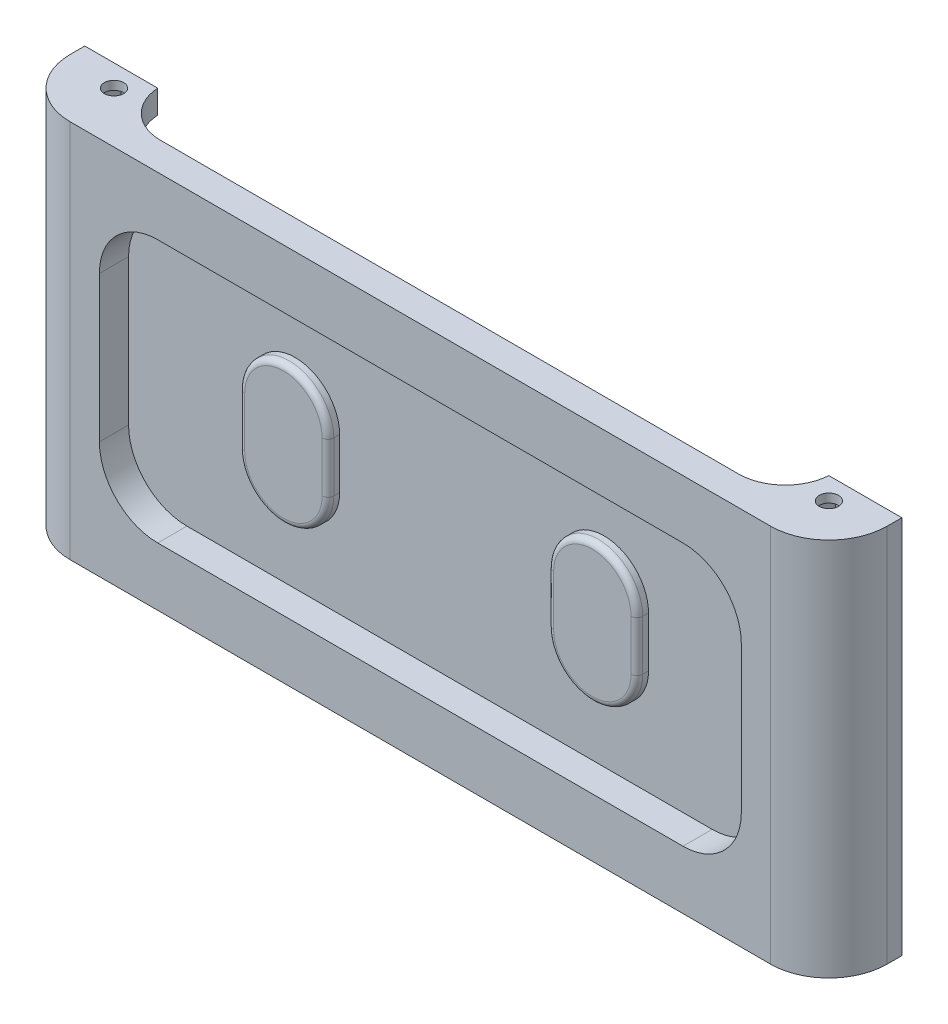
SolidWorks part; units mm, degrees
ref_plane "Front Plane" through (0, 0, 0) normal (0, 0, 1) x (1, 0, 0)
ref_plane "Top Plane" through (0, 0, 0) normal (0, 1, 0) x (1, 0, 0)
ref_plane "Right Plane" through (0, 0, 0) normal (1, 0, 0) x (0, 0, -1)
sketch "Sketch1" plane through (0, 0, 0) normal (0, 0, 1) x (1, 0, 0)
  line L1 (0, 0) -> (140, 0)
  line L2 (0, 0) -> (0, 65)
  line L3 (0, 65) -> (140, 65)
  line L4 (140, 0) -> (140, 65)
  dimension "D1" = 140
  dimension "D2" = 65
extrude "Boss-Extrude1" add sketch "Sketch1" along normal blind 12.5
sketch "Sketch4" plane through (0, 65, 0) normal (0, 1, 0) x (1, 0, 0)
  line L6 (5, 0) -> (135, 0)
  line L9 (135, 0) -> (135, -7.5)
  line L10 (5, -7.5) -> (5, 0)
  line L11 (135, -7.5) -> (5, -7.5)
  line L12 (135, 0) -> (135, -7.5)
  line L13 (5, -7.5) -> (5, 0)
  line L14 (135, -7.5) -> (5, -7.5)
  dimension "D1" = 5
extrude "Cut-Extrude3" cut sketch "Sketch4" against normal through all
sketch "Sketch2" plane through (0, 0, 12.5) normal (0, 0, 1) x (1, 0, 0)
  line L0 (70, 65) -> (70, 0) construction
  line L1 (140, 65) -> (0, 65) construction
  line L2 (0, 0) -> (140, 0) construction
  line L3 (140, 0) -> (140, 65) construction
  line L4 (15, 55) -> (125, 55)
  line L5 (15, 55) -> (15, 10)
  line L6 (15, 10) -> (125, 10)
  line L7 (125, 55) -> (125, 10)
  line L8 (15, 55) -> (125, 10) construction
  line L9 (15, 10) -> (125, 55) construction
  point P6 (70, 32.5)
  dimension "D1" = 15
  dimension "D2" = 10
extrude "Cut-Extrude1" cut sketch "Sketch2" against normal through all
fillet "Fillet1" radius 10 4 edges at (15, 10, 10) (15, 55, 10) (125, 10, 10) (125, 55, 10)
fillet "Fillet2" radius 10 2 edges at (140, 32.5, 12.5) (0, 32.5, 12.5)
sketch "Sketch5" plane through (0, 0, 0) normal (0, -1, 0) x (1, 0, 0)
  line L0 (0, 0) -> (5, 0) construction
  line L1 (5, 7.5) -> (12.5, 7.5)
  line L2 (5, 7.5) -> (5, 0)
  line L3 (5, 0) -> (12.5, 0)
  line L4 (12.5, 7.5) -> (12.5, 0)
  line L5 (135, 7.5) -> (127.5, 7.5)
  line L6 (135, 7.5) -> (135, 0)
  line L7 (135, 0) -> (127.5, 0)
  line L8 (127.5, 7.5) -> (127.5, 0)
extrude "Boss-Extrude2" add sketch "Sketch5" against normal blind 4
sketch "Sketch6" plane through (0, 4, 0) normal (0, 1, 0) x (1, 0, 0)
  line L0 (8.75, 0) -> (8.75, -7.5) construction
  line L1 (11.9254, -3.75) -> (10.3377, -1)
  line L2 (10.3377, -1) -> (7.1623, -1)
  line L3 (7.1623, -1) -> (5.5746, -3.75)
  line L4 (5.5746, -3.75) -> (7.1623, -6.5)
  line L5 (7.1623, -6.5) -> (10.3377, -6.5)
  line L6 (10.3377, -6.5) -> (11.9254, -3.75)
  line L7 (5, 0) -> (12.5, 0) construction
  line L8 (12.5, -7.5) -> (5, -7.5) construction
  line L9 (70, -12.5) -> (70, 1.5241) construction
  line L10 (130, -12.5) -> (10, -12.5) construction
  line L11 (134.4254, -3.75) -> (132.8377, -6.5)
  line L12 (132.8377, -6.5) -> (129.6623, -6.5)
  line L13 (129.6623, -6.5) -> (128.0746, -3.75)
  line L14 (128.0746, -3.75) -> (129.6623, -1)
  line L15 (129.6623, -1) -> (132.8377, -1)
  line L16 (132.8377, -1) -> (134.4254, -3.75)
  circle A0 centre (8.75, -3.75) radius 2.75 construction
  circle A1 centre (8.75, -3.75) radius 1.65
  circle A2 centre (131.25, -3.75) radius 1.65
  dimension "D1" = 3.3
  dimension "D2" = 5.5
extrude "Cut-Extrude5" cut sketch "Sketch6<2>" against normal through all contours A1 | A2 region at (8.75, 4, 3.75) region at (131.25, 4, 3.75)
sketch "Sketch6<2>" plane through (0, 4, 0) normal (0, 1, 0) x (1, 0, 0) same geometry as "Sketch6"
extrude "Cut-Extrude4" cut sketch "Sketch6" against normal blind 2.5
fillet "Fillet3" radius 8 2 edges at (127.5, 2, 7.5) (12.5, 2, 7.5)
ref_plane "Plane1" through (0, 32.5, 0) normal (0, 1, 0) x (1, 0, 0)
mirror "Mirror1" about plane through (0, 32.5, 0) normal (0, 1, 0) of "Cut-Extrude5", "Cut-Extrude4", "Boss-Extrude2", "Fillet3"
sketch "Sketch7" plane through (0, 0, 7.5) normal (0, 0, -1) x (-1, 0, 0)
  line L1 (-135, 61) -> (-5, 61)
  line L2 (-135, 61) -> (-135, 4)
  line L3 (-135, 4) -> (-5, 4)
  line L4 (-5, 61) -> (-5, 4)
extrude "Boss-Extrude3" add sketch "Sketch7" along normal blind 1 separate body
sketch "Sketch8" plane through (0, 0, 7.5) normal (0, 0, 1) x (1, 0, 0)
  line L0 (70, 55) -> (70, 24.7719) construction
  line L1 (115, 55) -> (25, 55) construction
  line L2 (25, 10) -> (115, 10) construction
  line L3 (43.5327, 36.6686) -> (96.4673, 36.6686) construction
  line L5 (70, 19.7719) -> (70, 10) construction
  line L6 (43.5327, 28.0667) -> (96.4673, 28.0667) construction
  line L7 (35.901, 36.6686) -> (35.901, 28.0667)
  line L8 (51.1643, 36.6686) -> (51.1643, 28.0667)
  line L9 (88.8357, 36.6686) -> (88.8357, 28.0667)
  line L10 (104.099, 36.6686) -> (104.099, 28.0667)
  arc A0 (51.1643, 36.6686) -> (35.901, 36.6686) centre (43.5327, 36.6686) ccw
  arc A1 (104.099, 36.6686) -> (88.8357, 36.6686) centre (96.4673, 36.6686) ccw
  arc A2 (35.901, 28.0667) -> (51.1643, 28.0667) centre (43.5327, 28.0667) ccw
  arc A3 (88.8357, 28.0667) -> (104.099, 28.0667) centre (96.4673, 28.0667) ccw
  point P11 (70, 36.6686)
extrude "Boss-Extrude4" add sketch "Sketch8" along normal blind 2 separate body contours A0 | A1 region at (43.5327, 32.3677, 7.5) region at (96.4673, 32.3677, 7.5)
sketch "Sketch9" plane through (0, 0, 6.5) normal (0, 0, -1) x (-1, 0, 0)
  line L0 (-19, 0) -> (-19, 42.7) construction
  line L1 (-20.4844, 0) -> (-119.5156, 0) construction
  line L2 (0, 0) -> (-19, 0) construction
  line L3 (-70, 65) -> (-70, 0) construction
  line L4 (-20.4844, 65) -> (-119.5156, 65) construction
  circle A0 centre (-19, 42.7) radius 8.4
  circle A1 centre (-121, 42.7) radius 8.4
  dimension "D3" = 16.8
  dimension "D1" = 19
  dimension "D2" = 42.7
extrude "Boss-Extrude6" add sketch "Sketch9" along normal blind 10 separate body
combine bodies "Combine1" operation type add bodies to combine 116 110 117
chamfer "Chamfer1" distance 3 angle 45 2 edges at (10.6, 42.7, 6.5) (112.6, 42.7, 6.5)
fillet "Fillet5" radius 1 2 edges at (10.6, 42.7, -3.5) (129.4, 42.7, -3.5)
fillet "Fillet6" radius 1 4 edges at (96.4673, 44.3003, 9.5) (104.099, 32.3677, 9.5) (96.4673, 20.4351, 9.5) (88.8357, 32.3677, 9.5)
fillet "Fillet7" radius 1 4 edges at (43.5327, 44.3003, 9.5) (51.1643, 32.3677, 9.5) (43.5327, 20.4351, 9.5) (35.901, 32.3677, 9.5)
